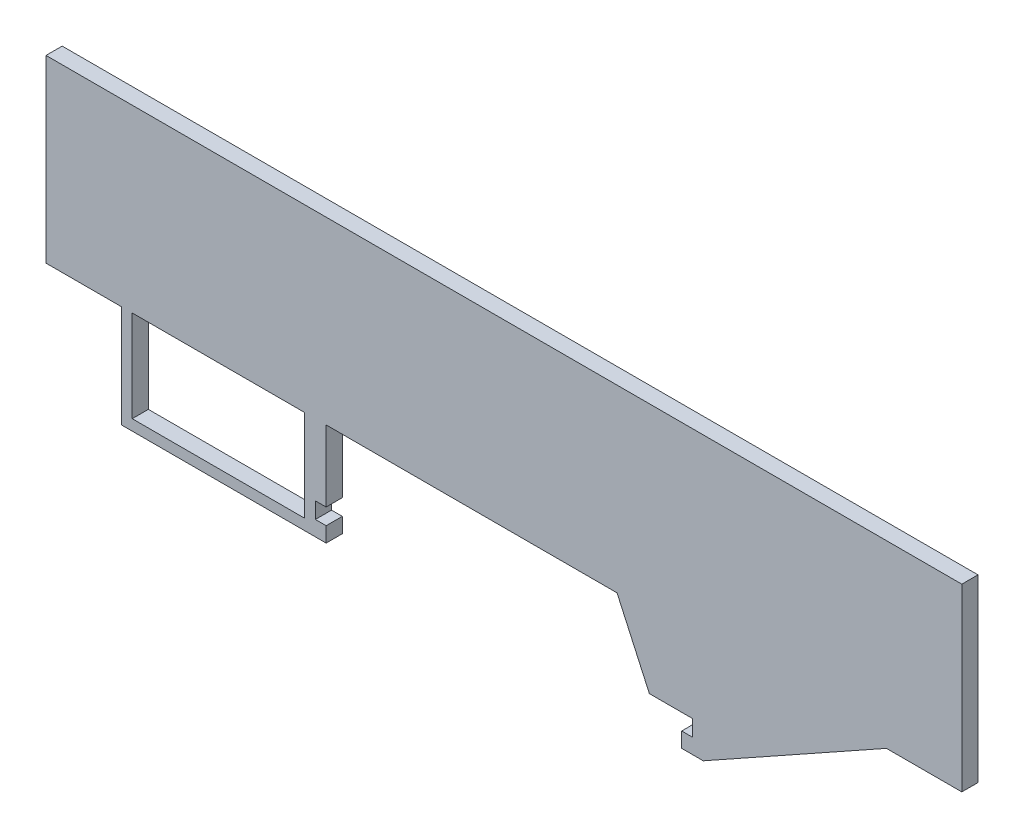
SolidWorks part; units mm, degrees
ref_plane "Front Plane" through (0, 0, 0) normal (0, 0, 1) x (1, 0, 0)
ref_plane "Top Plane" through (0, 0, 0) normal (0, 1, 0) x (1, 0, 0)
ref_plane "Right Plane" through (0, 0, 0) normal (1, 0, 0) x (0, 0, -1)
sketch "Sketch1" plane through (0, 0, 0) normal (0, 0, 1) x (1, 0, 0)
  line L1 (-42.5, 23.3) -> (42.5, 23.3)
  line L2 (-42.5, 23.3) -> (-42.5, 6.6)
  line L4 (42.5, 23.3) -> (42.5, 6.6)
  line L15 (42.5, 6.6) -> (-42.5, 6.6) construction
  line L16 (0, 23.3) -> (0, 0) construction
  line L17 (42.5, 6.6) -> (35.5, 6.6)
  line L18 (35.5, 6.6) -> (18.5, -2.9)
  line L19 (18.5, -2.9) -> (16.5, -2.9)
  line L20 (16.5, -2.9) -> (16.5, -1.5)
  line L21 (16.5, -1.5) -> (17.5, -1.5)
  line L22 (17.5, -1.5) -> (17.5, 0)
  line L23 (17.5, 0) -> (13.5, 0)
  line L24 (13.5, 0) -> (10.5, 6.6)
  line L25 (10.5, 6.6) -> (-16.5, 6.6)
  line L26 (-16.5, 6.6) -> (-16.5, 0)
  line L27 (-16.5, 0) -> (-17.5, 0)
  line L28 (-17.5, 0) -> (-17.5, -1.5)
  line L29 (-17.5, -1.5) -> (-16.5, -1.5)
  line L30 (-16.5, -1.5) -> (-16.5, -2.9)
  line L31 (-16.5, -2.9) -> (-35.5, -2.9)
  line L32 (-35.5, -2.9) -> (-35.5, 6.6)
  line L33 (-35.5, 6.6) -> (-42.5, 6.6)
  line L34 (-34.5, 6.6) -> (-34.5, -1.9)
  line L35 (-34.5, -1.9) -> (-18.5, -1.9)
  line L36 (-18.5, -1.9) -> (-18.5, 6.6)
  line L37 (-18.5, 6.6) -> (-34.5, 6.6)
  line L38 (-17.5, 0) -> (17.5, 0) construction
  point P9 (-0.601, 7.4271)
  point P12 (0, 0)
  dimension "D1" = 85
  dimension "D2" = 16.7
  dimension "D3" = 9.5
  dimension "D4" = 1.5
  dimension "D5" = 1.4
  dimension "D6" = 35
  dimension "D7" = 1
  dimension "D8" = 1
  dimension "D9" = 4
  dimension "D10" = 7
  dimension "D11" = 7
  dimension "D12" = 1
  dimension "D13" = 1
  dimension "D14" = 1
  dimension "D15" = 32
  dimension "D16" = 2
extrude "Boss-Extrude1" add sketch "Sketch1" along normal blind 1.5
ref_plane "Plane1" through (0, 0, 0) normal (1, 0, 0) x (0, 0, -1)
